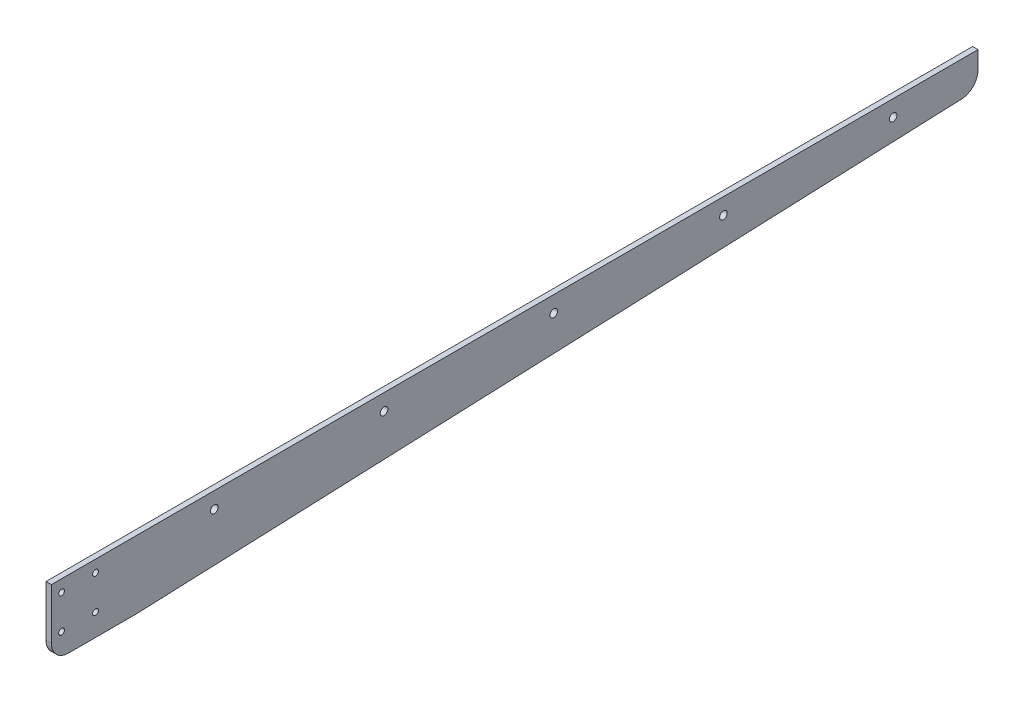
SolidWorks part; units mm, degrees
ref_plane "Front Plane" through (0, 0, 0) normal (0, 0, 1) x (1, 0, 0)
ref_plane "Top Plane" through (0, 0, 0) normal (0, 1, 0) x (1, 0, 0)
ref_plane "Right Plane" through (0, 0, 0) normal (1, 0, 0) x (0, 0, -1)
sketch "Sketch1" plane through (0, 0, 0) normal (1, 0, 0) x (0, 0, -1)
  line L0 (0, 0) -> (0, 40)
  line L1 (546, 40) -> (546, 20)
  line L2 (546, 20) -> (50, 0)
  line L3 (50, 0) -> (0, 0)
  line L4 (0, 40) -> (546, 40)
  dimension "D1" = 546
  dimension "D2" = 40
  dimension "D3" = 50
  dimension "D4" = 20
extrude "Boss-Extrude1" add sketch "Sketch1" along normal blind 3.175
hole_wizard "M3 Clearance Hole1" positions "3DSketch1" profile "Sketch3" hole size "M3" standard "ANSI Metric" end condition through all
sketch3d "3DSketch1"
  line L0 (3.175, 40, -6) -> (3.175, 0, -6) construction
  line L1 (3.175, 40, -546) -> (3.175, 40, 0) construction
  line L2 (3.175, 0, 0) -> (3.175, 0, -50) construction
  line L3 (3.175, 0, -26) -> (3.175, 40, -26) construction
  line L4 (3.175, 40, 0) -> (3.175, 0, 0) construction
  line L5 (3.175, 33, -6) -> (3.175, 13, -6) construction
  point P0 (3.175, 33, -26)
  point P11 (3.175, 33, -6)
  point P13 (3.175, 13, -26)
  point P15 (3.175, 13, -6)
  dimension "D1" = 20
  dimension "D2" = 20
  dimension "D3" = 6
  dimension "D4" = 7
sketch "Sketch3" plane through (3.175, 33, -26) normal (0, 1, 0) x (0, 0, -1)
  line L0 (0, 0) -> (0, 3.175)
  line L1 (0, 3.175) -> (1.7, 3.175)
  line L2 (1.7, 3.175) -> (1.7, 0)
  line L5 (1.7, 0) -> (0, 0)
  line L11 (0, -6.35) -> (0, 107.95) construction
  dimension "Thru Hole Dia." = 3.4
  dimension "Thru Hole Depth" = 3.175
fillet "Fillet1" radius 10 3 edges at (1.5875, 0, -50) (1.5875, 0, 0) (1.5875, 20, -546)
hole_wizard "#8 Clearance Hole1" positions "3DSketch2" profile "Sketch4" hole size "#8" standard "ANSI Inch" end condition through all
sketch3d "3DSketch2"
  line L0 (3.175, 29.6049, -546) -> (3.175, 40, -546) construction
  line L1 (3.175, 40, -546) -> (3.175, 40, 0) construction
  point P0 (3.175, 30.475, -496)
  dimension "D1" = 50
  dimension "D2" = 9.525
sketch "Sketch4" plane through (3.175, 30.475, -496) normal (0, 1, 0) x (0, 0, -1)
  line L0 (0, 0) -> (0, 3.175)
  line L1 (0, 3.175) -> (2.2479, 3.175)
  line L2 (2.2479, 3.175) -> (2.2479, 0)
  line L5 (2.2479, 0) -> (0, 0)
  line L11 (0, -6.35) -> (0, 107.95) construction
  dimension "Thru Hole Dia." = 4.4958
  dimension "Thru Hole Depth" = 3.175
pattern_linear "LPattern1" count 5 spacing 100 along (0, 0, 1) of "#8 Clearance Hole1"
